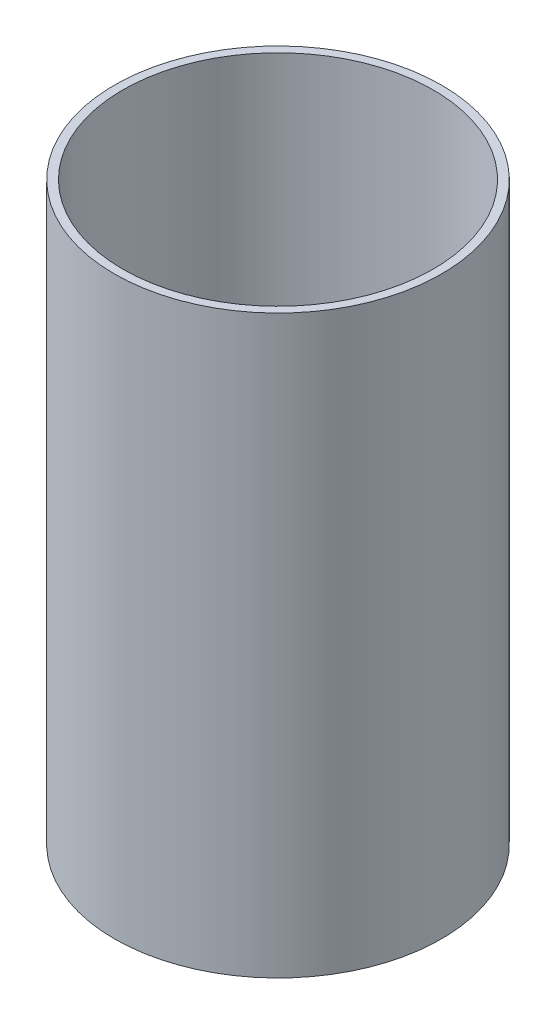
SolidWorks part; units mm, degrees
material "PVC Rigid"
ref_plane "Front Plane" through (0, 0, 0) normal (0, 0, 1) x (1, 0, 0)
ref_plane "Top Plane" through (0, 0, 0) normal (0, 1, 0) x (1, 0, 0)
ref_plane "Right Plane" through (0, 0, 0) normal (1, 0, 0) x (0, 0, -1)
sketch "Sketch1" plane through (0, 0, 0) normal (0, 1, 0) x (1, 0, 0)
  circle A0 centre (0, 0) radius 93.6625
  circle A1 centre (0, 0) radius 88.9
  dimension "D1" = 187.325
  dimension "D2" = 177.8
extrude "Boss-Extrude1" add sketch "Sketch1" along normal mid plane 329.7555
